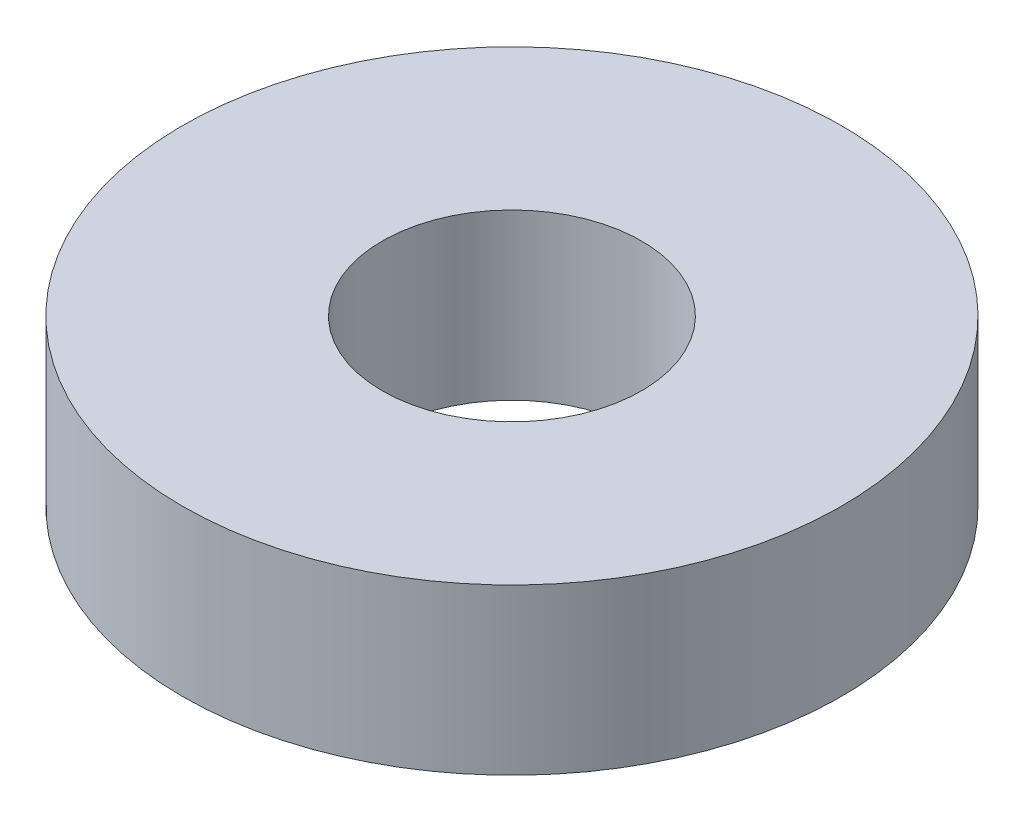
SolidWorks part; units mm, degrees
material "ABS"
ref_plane "Front Plane" through (0, 0, 0) normal (0, 0, 1) x (1, 0, 0)
ref_plane "Top Plane" through (0, 0, 0) normal (0, 1, 0) x (1, 0, 0)
ref_plane "Right Plane" through (0, 0, 0) normal (1, 0, 0) x (0, 0, -1)
ref_axis "x-axis" through (88.99, 0, 0) along (-1, 0, 0)
ref_axis "y-axis" through (0, 0, 55) along (0, 0, -1)
ref_axis "z-axis" through (0, 55, 0) along (0, -1, 0)
sketch "Sketch1" plane through (0, 0, 0) normal (0, 1, 0) x (1, 0, 0)
  circle A0 centre (0, 0) radius 6.35
  dimension "D1" = 12.7
extrude "wheelbase" add sketch "Sketch1" along normal mid plane 3.175
sketch "Sketch3" plane through (0, 1.5875, 0) normal (0, 1, 0) x (1, 0, 0)
  circle A0 centre (0, 0) radius 2.5
  dimension "D1" = 5
extrude "circlefit" cut sketch "Sketch3" against normal through all
sketch "Sketch4" plane through (0, 1.5875, 0) normal (0, 1, 0) x (1, 0, 0)
  line L0 (-1.5, 2) -> (1.5, 2)
  circle A0 centre (0, 0) radius 2.5 construction
  arc A1 (-1.5, 2) -> (1.5, 2) centre (0, 0) cw
  dimension "key1" = 2
extrude "gm26fit1" [suppressed] add sketch "Sketch4" against normal up to surface (3.175 mm away)
sketch "Sketch5" [suppressed] plane through (0, 1.5875, 0) normal (0, 1, 0) x (1, 0, 0)
  line L0 (-1.5, -2) -> (1.5, -2)
  line L1 (-1.5, 2) -> (1.5, 2) construction
  arc A0 (-1.5, 2) -> (1.5, 2) centre (0, 0) ccw construction
  arc A1 (-1.5, -2) -> (1.5, -2) centre (0, 0) ccw
  dimension "key2" = 4
extrude "gm26fit2" [suppressed] add sketch "Sketch5" against normal up to surface (3.175 mm away)
equation "\"key2@Sketch5\" = \"key1@Sketch4\"*2"
